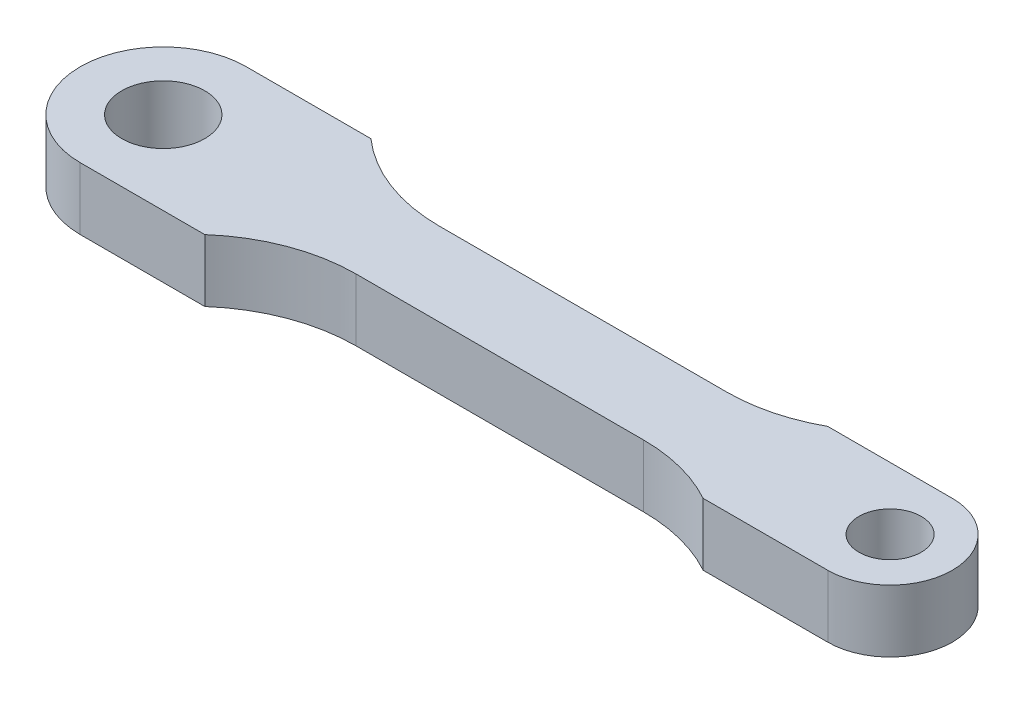
SolidWorks part; units mm, degrees
material "1023 Carbon Steel Sheet (SS)"
ref_plane "Front Plane" through (0, 0, 0) normal (0, 0, 1) x (1, 0, 0)
ref_plane "Top Plane" through (0, 0, 0) normal (0, 1, 0) x (1, 0, 0)
ref_plane "Right Plane" through (0, 0, 0) normal (1, 0, 0) x (0, 0, -1)
sketch "Sketch1" plane through (0, 0, 0) normal (0, 1, 0) x (1, 0, 0)
  line L0 (-17.5, 0) -> (17.5, 0) construction
  line L1 (-17.5, 4) -> (-11.5, 4)
  line L2 (-17.5, -4) -> (-11.5, -4)
  line L3 (17.5, 3) -> (11.5, 3)
  line L4 (17.5, -3) -> (11.5, -3)
  line L5 (-6.2085, 2) -> (7.627, 2)
  line L6 (-6.2085, -2) -> (7.627, -2)
  circle A0 centre (-17.5, 0) radius 4
  circle A1 centre (17.5, 0) radius 3
  arc A2 (-6.2085, -2) -> (-11.5, -4) centre (-6.2085, -10) ccw
  arc A3 (-6.2085, 2) -> (-11.5, 4) centre (-6.2085, 10) cw
  arc A4 (7.627, 2) -> (11.5, 3) centre (7.627, 10) ccw
  arc A5 (7.627, -2) -> (11.5, -3) centre (7.627, -10) cw
  circle A6 centre (-17.5, 0) radius 2
  circle A7 centre (17.5, 0) radius 1.5
  dimension "D1" = 8
  dimension "D2" = 6
  dimension "D7" = 8
  dimension "D8" = 8
  dimension "D9" = 4
  dimension "D10" = 3
  dimension "D3" = 35
  dimension "D4" = 6
  dimension "D5" = 6
  dimension "D6" = 4
extrude "Boss-Extrude1" add sketch "Sketch1" along normal mid plane 3 contours A6 A0 | A0 L0 A1 L3 A4 L5 A3 L1 | L0 A0 L2 A2 L6 A5 L4 A1 | A1 A7 | A1 region at (-14.7516, 0, 2.7484) region at (-0.3273, 0, -1.4004) region at (-0.3273, 0, 1.4004) region at (15.4387, 0, -2.0613)
extrude "Cut-Extrude1" cut sketch "Sketch1<4>" against normal through all both and the other way through all contours A7
sketch "Sketch1<4>" plane through (0, 0, 0) normal (0, 1, 0) x (1, 0, 0) same geometry as "Sketch1"
